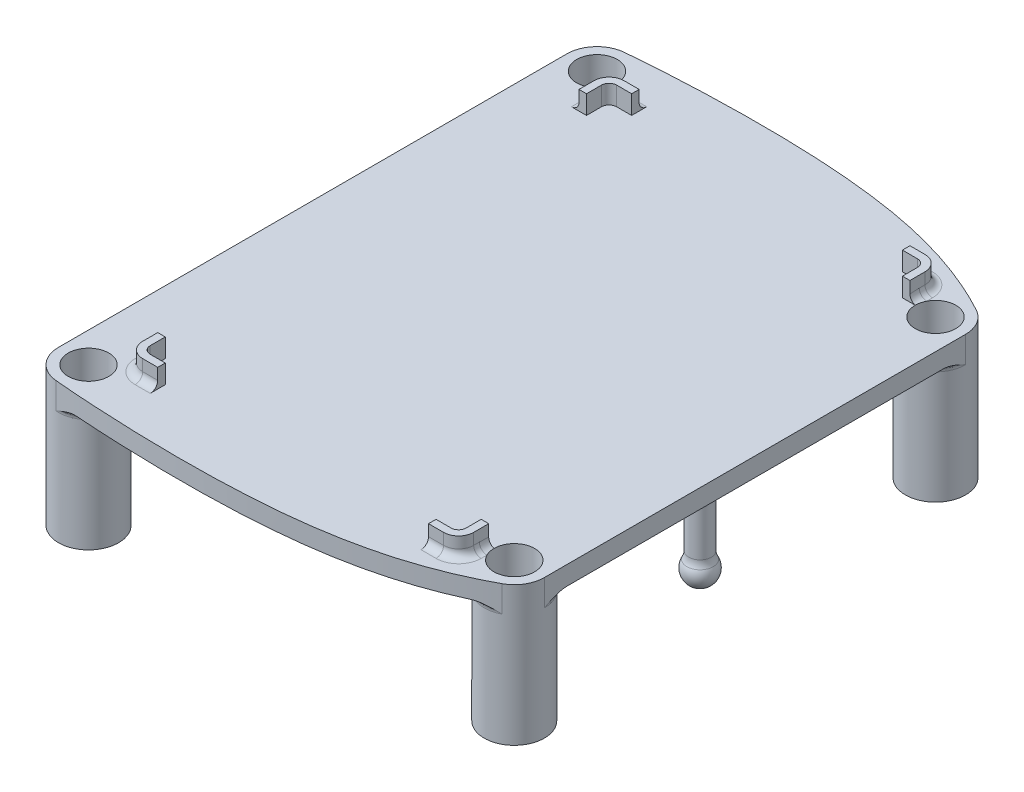
SolidWorks part; units mm, degrees
ref_plane "前视基准面" through (0, 0, 0) normal (0, 0, 1) x (1, 0, 0)
ref_plane "上视基准面" through (0, 0, 0) normal (0, 1, 0) x (1, 0, 0)
ref_plane "右视基准面" through (0, 0, 0) normal (1, 0, 0) x (0, 0, -1)
other "Configuration Table"
sketch "草图1" plane through (0, 0, 0) normal (0, 1, 0) x (1, 0, 0)
  line L0 (0, 35.4779) -> (0, -35.3561) construction
  line L1 (-47.5, 31) -> (-41.5, 31)
  line L2 (-47.5, 25) -> (-47.5, -25)
  line L3 (-47.5, -31) -> (-41.5, -31)
  line L4 (47.5, 25) -> (47.5, -25)
  line L5 (-47.5, 31) -> (47.5, -31) construction
  line L6 (-47.5, -31) -> (47.5, 31) construction
  line L9 (-41.5, 31) -> (-41.5, 41)
  line L11 (-29.5, 31) -> (-29.5, 41)
  line L12 (29.5, 31) -> (29.5, 41)
  line L14 (41.5, 31) -> (41.5, 41)
  line L15 (-78.7463, 0) -> (58.6748, 0) construction
  line L16 (41.5, -31) -> (41.5, -41)
  line L18 (29.5, -31) -> (29.5, -41)
  line L21 (-29.5, -31) -> (-29.5, -41)
  line L23 (-41.5, -31) -> (-41.5, -41)
  line L24 (-29.5, 31) -> (-3, 31)
  line L25 (41.5, 31) -> (47.5, 31)
  line L26 (41.5, -31) -> (47.5, -31)
  line L27 (-29.5, -31) -> (-3, -31)
  line L28 (47.5, 31) -> (50.8, 31)
  line L29 (-47.5, 31) -> (-50.8, 31)
  line L31 (-47.5, 25) -> (-50.8, 25)
  line L33 (47.5, 25) -> (50.8, 25)
  line L36 (47.5, -25) -> (50.8, -25)
  line L37 (47.5, -31) -> (50.8, -31)
  line L38 (-47.5, -31) -> (-50.8, -31)
  line L39 (-47.5, -25) -> (-50.8, -25)
  line L41 (-3, -33.8) -> (-3, -31)
  line L43 (-3, 33.8) -> (-3, 31)
  line L45 (3, 33.8) -> (3, 31)
  line L47 (3, -33.8) -> (3, -31)
  line L48 (3, 31) -> (29.5, 31)
  line L49 (3, -31) -> (29.5, -31)
  arc A0 (-41.5, 41) -> (-29.5, 41) centre (-35.5, 41) cw
  arc A1 (-41.5, -41) -> (-29.5, -41) centre (-35.5, -41) ccw
  arc A2 (41.5, -41) -> (29.5, -41) centre (35.5, -41) cw
  arc A3 (41.5, 41) -> (29.5, 41) centre (35.5, 41) ccw
  arc A4 (-50.8, 31) -> (-50.8, 25) centre (-50.8, 28) ccw
  circle A5 centre (-50.8, 28) radius 1.5
  circle A6 centre (50.8, 28) radius 1.5
  arc A7 (50.8, 31) -> (50.8, 25) centre (50.8, 28) cw
  circle A8 centre (50.8, -28) radius 1.5
  arc A9 (50.8, -31) -> (50.8, -25) centre (50.8, -28) ccw
  circle A10 centre (-50.8, -28) radius 1.5
  arc A11 (-50.8, -31) -> (-50.8, -25) centre (-50.8, -28) cw
  arc A12 (-3, 33.8) -> (3, 33.8) centre (0, 33.8) cw
  circle A13 centre (0, 33.8) radius 1.5
  circle A14 centre (0, -33.8) radius 1.5
  arc A15 (-3, -33.8) -> (3, -33.8) centre (0, -33.8) ccw
  point P0 (0, 0)
  dimension "D8" = 2.8
  dimension "D1" = 95
  dimension "D2" = 62
  dimension "D3" = 83
  dimension "D4" = 12
  dimension "D5" = 10
  dimension "D6" = 3.3
  dimension "D7" = 6
  dimension "D9" = 6
extrude "凸台-拉伸1" add sketch "草图1" against normal blind 15
sketch "草图2" plane through (0, -15, 0) normal (0, -1, 0) x (1, 0, 0)
  line L0 (-63.1336, 0) -> (63.5579, 0) construction
  line L1 (-57.0239, 31) -> (-3, 31)
  line L2 (-57.0239, 31) -> (-57.0239, 48.5806)
  line L3 (-57.0239, 48.5806) -> (57.0239, 48.5806)
  line L4 (57.0239, 31) -> (57.0239, 48.5806)
  line L5 (0, 56.9992) -> (0, -44.1169) construction
  line L6 (3, 33.8) -> (3, 31) construction
  line L7 (-3, 31) -> (-3, 33.8) construction
  line L8 (3, 33.8) -> (3, 31)
  line L9 (-3, 31) -> (-3, 33.8)
  line L10 (3, 31) -> (57.0239, 31)
  line L11 (3, -33.8) -> (3, -31)
  line L12 (-3, -31) -> (-3, -33.8)
  line L13 (-57.0239, -31) -> (-3, -31)
  line L14 (-57.0239, -31) -> (-57.0239, -48.5806)
  line L15 (-57.0239, -48.5806) -> (57.0239, -48.5806)
  line L16 (57.0239, -31) -> (57.0239, -48.5806)
  line L17 (3, -31) -> (57.0239, -31)
  arc A0 (3, 33.8) -> (-3, 33.8) centre (0, 33.8) ccw construction
  arc A1 (3, 33.8) -> (-3, 33.8) centre (0, 33.8) ccw
  arc A2 (3, -33.8) -> (-3, -33.8) centre (0, -33.8) cw
extrude "切除-拉伸1" cut sketch "草图2" against normal blind 11
sketch "草图3" plane through (0, -15, 0) normal (0, -1, 0) x (1, 0, 0)
  line L0 (47.5, 25) -> (47.5, -25) construction
  line L1 (-45, -28.5) -> (45, -28.5)
  line L2 (-45, -28.5) -> (-45, 28.5)
  line L3 (-45, 28.5) -> (45, 28.5)
  line L4 (45, -28.5) -> (45, 28.5)
  line L5 (-45, -28.5) -> (45, 28.5) construction
  line L6 (-45, 28.5) -> (45, -28.5) construction
  line L7 (-50.8, 31) -> (-3, 31) construction
  point P0 (0, 0)
  dimension "D1" = 2.5
  dimension "D2" = 2.5
extrude "切除-拉伸2" cut sketch "草图3" against normal blind 12
sketch "草图4" plane through (0, -4, 0) normal (0, -1, 0) x (1, 0, 0)
  line L0 (-29.5, 41) -> (-41.5, 41) construction
  line L1 (-71.7869, 0) -> (71.1524, 0) construction
  line L2 (0, 61.1393) -> (0, -47.8922) construction
  circle A0 centre (-35.5, 41) radius 2.8
  circle A1 centre (35.5, 41) radius 2.8
  circle A2 centre (35.5, -41) radius 2.8
  circle A3 centre (-35.5, -41) radius 2.8
extrude "凸台-拉伸2" add sketch "草图4" along normal blind 3.3 separate body
sketch "草图5" plane through (0, -7.3, 0) normal (0, -1, 0) x (1, 0, 0)
  line L0 (-58.868, 0) -> (56.1189, 0) construction
  line L1 (0, 46.5823) -> (0, -51.4835) construction
  circle A0 centre (-35.5, 41) radius 1.5
  circle A1 centre (35.5, 41) radius 1.5
  circle A2 centre (35.5, -41) radius 1.5
  circle A3 centre (-35.5, -41) radius 1.5
extrude "凸台-拉伸3" add sketch "草图5" along normal blind 1.3 separate body
sketch "草图6" plane through (0, -15, 0) normal (0, -1, 0) x (1, 0, 0)
  line L0 (-50.8, 31) -> (-3, 31) construction
  line L1 (-47.5, 31) -> (47.5, 31)
  line L2 (-47.5, 31) -> (-47.5, -31)
  line L3 (-47.5, -31) -> (47.5, -31)
  line L4 (47.5, 31) -> (47.5, -31)
  line L5 (50.8, -31) -> (3, -31) construction
extrude "切除-拉伸3" cut sketch "草图6" against normal blind 5
sketch "草图7" plane through (0, -3, 0) normal (0, -1, 0) x (1, 0, 0)
  line L0 (-60.2485, 0) -> (64.067, 0) construction
  line L1 (0, 41.3678) -> (0, -47.8169) construction
  line L2 (-30, -19) -> (30, -19)
  line L3 (-30, 21) -> (-2, 21)
  line L4 (-30, 21) -> (-30, 19)
  line L5 (-30, 19) -> (30, 19)
  line L6 (30, 21) -> (30, 19)
  line L7 (-30, 21) -> (30, 19) construction
  line L8 (-30, 19) -> (30, 21) construction
  line L9 (30, -21) -> (30, -19)
  line L10 (-30, -21) -> (-2, -21)
  line L11 (-30, -21) -> (-30, -19)
  line L12 (45, 28.5) -> (-45, 28.5) construction
  line L13 (-2, 28.5) -> (2, 28.5)
  line L14 (-2, 28.5) -> (-2, 21)
  line L16 (2, 28.5) -> (2, 21)
  line L18 (2, -28.5) -> (2, -21)
  line L19 (-2, -28.5) -> (2, -28.5)
  line L20 (-2, -28.5) -> (-2, -21)
  line L21 (2, 21) -> (30, 21)
  line L22 (2, -21) -> (30, -21)
  point P5 (0, 20)
  dimension "D1" = 19
  dimension "D2" = 2
  dimension "D3" = 60
  dimension "D4" = 4
extrude "凸台-拉伸4" add sketch "草图7" along normal blind 2.5 separate body
sketch "草图9" plane through (0, -10, 0) normal (0, -1, 0) x (1, 0, 0)
  line L0 (-45, 28.5) -> (45, 28.5) construction
  line L1 (41.5, 31) -> (32, 31)
  line L2 (41.5, 31) -> (41.5, 28.5)
  line L3 (41.5, 28.5) -> (32, 28.5)
  line L4 (32, 31) -> (32, 28.5)
  dimension "D1" = 9.5
extrude "切除-拉伸4" cut sketch "草图9" against normal blind 5
sketch "草图10" plane through (0, 0, 0) normal (0, 1, 0) x (1, 0, 0)
  line L1 (-34.25, -14) -> (34.25, -14)
  line L2 (-36.25, -12) -> (-36.25, 12)
  line L3 (-34.25, 14) -> (34.25, 14)
  line L4 (36.25, -12) -> (36.25, 12)
  line L5 (-36.25, -14) -> (36.25, 14) construction
  line L6 (-36.25, 14) -> (36.25, -14) construction
  arc A0 (-34.25, -14) -> (-36.25, -12) centre (-34.25, -12) cw
  arc A1 (34.25, -14) -> (36.25, -12) centre (34.25, -12) ccw
  arc A2 (34.25, 14) -> (36.25, 12) centre (34.25, 12) cw
  arc A3 (-36.25, 12) -> (-34.25, 14) centre (-34.25, 12) cw
  point P0 (0, 0)
  dimension "D3" = 2
  dimension "D1" = 72.5
  dimension "D2" = 28
extrude "切除-拉伸5" cut sketch "草图10" against normal through all
fillet "圆角1" radius 3 8 edges at (41.5, -2, 31) (29.5, -2, 31) (-29.5, -2, 31) (-41.5, -2, 31) (-41.5, -2, -31) (-29.5, -2, -31) (29.5, -2, -31) (41.5, -2, -31)
fillet "圆角3" radius 1 12 edges at (0, -3, -28.5) (-45, -3, 0) (0, -3, 28.5) (45, -3, 0) (-35.6642, -3, -13.4142) (0, -3, -14) (35.6642, -3, -13.4142) (36.25, -3, 0) (35.6642, -3, 13.4142) (0, -3, 14) (-35.6642, -3, 13.4142) (-36.25, -3, 0)
combine bodies "组合1" operation type add bodies to combine 111 121 115 109 112 113 116 110 118 119 114
fillet "圆角4" radius 1 40 edges at (-2, -3, 24.25) (-2, -3, -24.25) (-2, -3.2929, 28.2071) (-2, -3.2929, -28.2071) (-2, -4.75, 28.5) (-2, -4.75, -28.5) (-2, -5.5, 24.75) (-30, -3, 20) (16, -5.5, 21) (0, -5.5, 28.5) (-30, -3, -20) (-2, -5.5, -24.75) (0, -5.5, -28.5) (16, -5.5, -21) (-2, -4.25, 21) (-16, -5.5, 21) (-30, -4.25, 21) (-16, -3, 21) (2, -4.25, 21) (2, -5.5, 24.75) (2, -4.75, 28.5) (2, -3.2929, 28.2071) (2, -3, 24.25) (-30, -4.25, -21) (-16, -5.5, -21) (-2, -4.25, -21) (-16, -3, -21) (2, -5.5, -24.75) (2, -4.25, -21) (2, -3, -24.25) (2, -3.2929, -28.2071) (2, -4.75, -28.5) (-47.5, -5, 25) (-47.5, -5, -25) (-3, -5, -31) (3, -5, -31) (47.5, -5, -25) (47.5, -5, 25) (-3, -5, 31) (3, -5, 31)
sketch "草图11" plane through (0, 0, 0) normal (0, 1, 0) x (1, 0, 0)
  line L0 (-69.2433, 0) -> (76.7956, 0) construction
  circle A0 centre (0, 33.8) radius 4
  circle A1 centre (50.8, 28) radius 4
  circle A2 centre (0, -33.8) radius 4
  circle A3 centre (50.8, -28) radius 4
extrude "凸台-拉伸5" add sketch "草图11" along normal blind 16
sketch "草图12" plane through (0, 16, 0) normal (0, 1, 0) x (1, 0, 0)
  line L0 (-65.6793, 0) -> (77.8139, 0) construction
  circle A0 centre (0, 33.8) radius 1.5
  circle A1 centre (50.8, 28) radius 1.5
  circle A2 centre (0, -33.8) radius 1.5
  circle A3 centre (50.8, -28) radius 1.5
extrude "切除-拉伸6" cut sketch "草图12" against normal up to next
sketch "草图13" plane through (0, 16, 0) normal (0, 1, 0) x (1, 0, 0)
  line L0 (-55.9061, 0) -> (58.1408, 0) construction
  circle A0 centre (0, 33.8) radius 2.7
  circle A1 centre (50.8, 28) radius 2.7
  circle A2 centre (0, -33.8) radius 2.7
  circle A3 centre (50.8, -28) radius 2.7
extrude "切除-拉伸7" cut sketch "草图13" against normal blind 12.5
sketch "草图14" plane through (0, 16, 0) normal (0, 1, 0) x (1, 0, 0)
  line L0 (0, 33.8) -> (0, -33.8) construction
  line L1 (50.8, 28) -> (50.8, -28) construction
  line L2 (-60.003, 0) -> (68.6402, 0) construction
  line L3 (0, 33.8) -> (0, -33.8)
  line L4 (0, 33.8) -> (12.6031, 34.95) construction
  line L5 (12.6031, 34.95) -> (27.419, 34.7819) construction
  line L6 (27.419, 34.7819) -> (38.9454, 34.4297) construction
  line L7 (38.9454, 34.4297) -> (50.8, 28) construction
  line L8 (50.8, 28) -> (50.8, -28)
  line L9 (0, -33.8) -> (12.6031, -34.95) construction
  line L10 (12.6031, -34.95) -> (27.419, -34.7819) construction
  line L11 (27.419, -34.7819) -> (38.9454, -34.4297) construction
  line L12 (38.9454, -34.4297) -> (50.8, -28) construction
  line L13 (54.8, 28) -> (54.8, -28)
  line L14 (-4, 33.8) -> (-4, -33.8)
  line L15 (-4, 37.4516) -> (-4, -37.4516) construction
  line L16 (54.8, 30.381) -> (54.8, -30.381) construction
  arc A0 (3.9878, 34.1116) -> (3.9835, 34.1635) centre (0, 33.8) ccw
  arc A1 (52.7071, -31.5161) -> (54.8, -28) centre (50.8, -28) ccw
  arc A2 (3.9835, -34.1635) -> (3.9878, -34.1116) centre (0, -33.8) ccw
  circle A8 centre (50.8, 28) radius 1.5 construction
  circle A9 centre (0, -33.8) radius 4 construction
  circle A11 centre (50.8, 28) radius 4 construction
  circle A12 centre (0, 33.8) radius 4 construction
  arc A13 (-4, -33.8) -> (0, -37.8) centre (0, -33.8) ccw
  arc A15 (54.8, 28) -> (52.7071, 31.5161) centre (50.8, 28) ccw
  arc A16 (-0.3635, 37.7835) -> (-4, 33.8) centre (0, 33.8) ccw
  spline S0 degree 4 poles (0, 33.8) (12.6031, 34.95) (27.419, 34.7819) (38.9454, 34.4297) (50.8, 28) knots 0 0 0 0 0 1 1 1 1 1
  spline S1 degree 4 poles (0, -33.8) (12.6031, -34.95) (27.419, -34.7819) (38.9454, -34.4297) (50.8, -28) knots 0 0 0 0 0 1 1 1 1 1
  spline S2 degree 1 poles (-4, -37.4516) (54.8, -30.381) knots 0 0 1 1 construction
  spline S3 degree 1 poles (-4, 37.4516) (54.8, 30.381) knots 0 0 1 1 construction
  spline S4 degree 3 poles (54.8, -30.381) (54.2486, -30.68) (53.6303, -31.0154) (52.9472, -31.3859) (52.7924, -31.4698) (52.565, -31.5933) (52.1027, -31.841) (51.093, -32.3627) (49.5916, -33.0832) (47.1986, -34.1154) (44.1982, -35.2065) (39.3793, -36.5763) (33.3024, -37.691) (25.8804, -38.3646) (18.3191, -38.5854) (11.9591, -38.5008) (6.9036, -38.2973) (3.2926, -38.0869) (0.8055, -37.8906) (-0.7075, -37.7519) (-1.3947, -37.6892) (-2.5351, -37.5854) (-3.4138, -37.5051) (-4, -37.4516) knots -0.072135 -0.072135 -0.072135 -0.072135 -0.037252 -0.032891 -0.029088 -0.026907 -0.01981 -0.002368 0.032515 0.067399 0.137166 0.206933 0.346467 0.486001 0.625535 0.765069 0.834836 0.904603 0.967642 0.976363 0.991812 1.009254 1.044138 1.044138 1.044138 1.044138 only from (52.7071, -31.5161) to (-0.3635, -37.7835)
  spline S5 degree 3 poles (-4, 37.4516) (-3.4138, 37.5051) (-2.5351, 37.5854) (-1.3947, 37.6892) (-0.7075, 37.7519) (0.8055, 37.8906) (3.2926, 38.0869) (6.9036, 38.2973) (11.9591, 38.5008) (18.3191, 38.5854) (25.8804, 38.3646) (33.3024, 37.691) (39.3793, 36.5763) (44.1982, 35.2065) (47.1986, 34.1154) (49.5916, 33.0832) (51.093, 32.3627) (52.1027, 31.841) (52.565, 31.5933) (52.7924, 31.4698) (52.9472, 31.3859) (53.6303, 31.0154) (54.2486, 30.68) (54.8, 30.381) knots -0.072135 -0.072135 -0.072135 -0.072135 -0.037252 -0.01981 -0.00436 0.00436 0.067399 0.137166 0.206933 0.346467 0.486001 0.625535 0.765069 0.834836 0.904603 0.939487 0.974371 0.991812 0.99891 1.00109 1.004894 1.009254 1.044138 1.044138 1.044138 1.044138 only from (-0.3635, 37.7835) to (52.7071, 31.5161)
  point P11 (50.8, 0)
  point P17 (0, 0)
  circle M17 centre (0, 33.8) radius 2.7
  circle M18 centre (0, 33.8) radius 4
  dimension "D1" = 4
extrude "凸台-拉伸6" add sketch "草图14" along normal blind 2.5 contours S5 S0 L8 S1 L3 L14 A13 S4 A1 L13 A15 M18 | L3 S1 L8 S0 M18 | S0 L3 M17 M18 | L3 S0 M17 | S0 L3 M17 M18 | S0 L3 M17 region at (1.1785, 16, -32.7167) region at (-0.4217, 16, -34.1876) region at (2.2186, 16, -31.7515) region at (-0.1131, 16, -30.45) region at (24.8986, 16, 0.1265) region at (-0.9694, 16, 2)
sketch "草图15" plane through (0, 18.5, 0) normal (0, 1, 0) x (1, 0, 0)
  line L2 (-4, 33.8) -> (-4, -33.8)
  line L3 (54.8, -28) -> (54.8, 28)
  line L4 (-4, 33.8) -> (-4, -33.8)
  line L5 (54.8, -28) -> (54.8, 28)
  circle A0 centre (0, 33.8) radius 2.7
  circle A1 centre (50.8, 28) radius 2.7
  circle A2 centre (50.8, -28) radius 2.7
  circle A3 centre (0, -33.8) radius 2.7
  arc A4 (-0.3635, 37.7835) -> (-4, 33.8) centre (0, 33.8) ccw
  arc A5 (-4, -33.8) -> (-0.3635, -37.7835) centre (0, -33.8) ccw
  arc A6 (52.7071, -31.5161) -> (54.8, -28) centre (50.8, -28) ccw
  arc A7 (54.8, 28) -> (52.7071, 31.5161) centre (50.8, 28) ccw
  arc A8 (-0.3635, 37.7835) -> (-4, 33.8) centre (0, 33.8) ccw
  arc A9 (-4, -33.8) -> (-0.3635, -37.7835) centre (0, -33.8) ccw
  arc A10 (52.7071, -31.5161) -> (54.8, -28) centre (50.8, -28) ccw
  arc A11 (54.8, 28) -> (52.7071, 31.5161) centre (50.8, 28) ccw
  spline S2 degree 3 poles (-2546.4981, 1528.7201) (61.493, 26.0185) (56.6767, 29.3897) (52.1027, 31.841) (51.093, 32.3627) (49.5916, 33.0832) (47.1986, 34.1154) (44.1982, 35.2065) (39.3793, 36.5763) (33.3024, 37.691) (25.8804, 38.3646) (18.3191, 38.5854) (11.9591, 38.5008) (6.9036, 38.2973) (3.2926, 38.0869) (-15.5497, 36.6001) (-30.0191, 32.3563) (2942.6396, 619.4497) knots -0.238757 -0.238757 -0.238757 -0.238757 0.00109 0.008188 0.025629 0.060513 0.095397 0.165164 0.234931 0.374465 0.513999 0.653533 0.793067 0.862834 0.932601 0.99564 1.935016 1.935016 1.935016 1.935016 only from (52.7071, 31.5161) to (-0.3635, 37.7835)
  spline S3 degree 3 poles (2942.5968, -619.4413) (-30.0189, -32.3564) (-15.5496, -36.6001) (3.2926, -38.0869) (6.9036, -38.2973) (11.9591, -38.5008) (18.3191, -38.5854) (25.8804, -38.3646) (33.3024, -37.691) (39.3793, -36.5763) (44.1982, -35.2065) (47.1986, -34.1154) (49.5916, -33.0832) (51.093, -32.3627) (52.1027, -31.841) (56.6765, -29.3898) (61.4926, -26.0188) (-2546.1335, -1528.51) knots -0.963009 -0.963009 -0.963009 -0.963009 -0.023637 0.039401 0.109168 0.178935 0.318469 0.458004 0.597538 0.737072 0.806839 0.876606 0.911489 0.946373 0.963815 0.970912 1.210749 1.210749 1.210749 1.210749 only from (-0.3635, -37.7835) to (52.7071, -31.5161)
  spline S4 degree 3 poles (52.7071, 31.5161) (52.6884, 31.5263) (52.5461, 31.6034) (52.1027, 31.841) (51.093, 32.3627) (49.5916, 33.0832) (47.1986, 34.1154) (44.1982, 35.2065) (39.3793, 36.5763) (33.3024, 37.691) (25.8804, 38.3646) (18.3191, 38.5854) (11.9591, 38.5008) (6.9036, 38.2973) (3.2926, 38.0869) (0.8821, 37.8967) (-0.2881, 37.7903) (-0.3635, 37.7835) knots 0 0 0 0 0.00109 0.008188 0.025629 0.060513 0.095397 0.165164 0.234931 0.374465 0.513999 0.653533 0.793067 0.862834 0.932601 0.99564 1 1 1 1
  spline S5 degree 3 poles (-0.3635, -37.7835) (-0.2881, -37.7903) (0.8821, -37.8967) (3.2926, -38.0869) (6.9036, -38.2973) (11.9591, -38.5008) (18.3191, -38.5854) (25.8804, -38.3646) (33.3024, -37.691) (39.3793, -36.5763) (44.1982, -35.2065) (47.1986, -34.1154) (49.5916, -33.0832) (51.093, -32.3627) (52.1027, -31.841) (52.5461, -31.6034) (52.6884, -31.5263) (52.7071, -31.5161) knots -0.027998 -0.027998 -0.027998 -0.027998 -0.023637 0.039401 0.109168 0.178935 0.318469 0.458004 0.597538 0.737072 0.806839 0.876606 0.911489 0.946373 0.963815 0.970912 0.972002 0.972002 0.972002 0.972002
  dimension "D1" = 0
extrude "切除-拉伸9" cut sketch "草图15" against normal up to next contours A0 | A1 | A3 | A2 region at (0, 18.5, -33.8) region at (50.8, 18.5, -28) region at (50.8, 18.5, 28) region at (0, 18.5, 33.8)
sketch "草图18" plane through (0, 18.5, 0) normal (0, 1, 0) x (1, 0, 0)
  line L0 (-4, 0) -> (54.8, 0) construction
  line L1 (-4, 33.8) -> (-4, -33.8) construction
  line L2 (54.8, 28) -> (54.8, -28) construction
  line L3 (3.4, 30) -> (3.4, -30)
  line L4 (5.4, 31) -> (45.4, 31)
  line L5 (4.4, 30) -> (4.4, -30)
  line L6 (5.4, -31) -> (45.4, -31)
  line L7 (46.4, 30) -> (46.4, -30)
  line L8 (4.4, 31) -> (46.4, -31) construction
  line L9 (4.4, -31) -> (46.4, 31) construction
  line L10 (5.4, -32) -> (45.4, -32)
  line L11 (47.4, 30) -> (47.4, -30)
  line L12 (5.4, 32) -> (45.4, 32)
  line L13 (7.4, 32) -> (7.4, 31)
  line L14 (3.4, 28) -> (4.4, 28)
  line L15 (7.4, -32) -> (7.4, -31)
  line L16 (3.4, -28) -> (4.4, -28)
  line L17 (25.4, 35.8449) -> (25.4, -33.7801) construction
  line L18 (47.4, -28) -> (46.4, -28)
  line L19 (43.4, -32) -> (43.4, -31)
  line L20 (47.4, 28) -> (46.4, 28)
  line L21 (43.4, 32) -> (43.4, 31)
  arc A0 (45.4, -31) -> (46.4, -30) centre (45.4, -30) ccw
  arc A1 (4.4, -30) -> (5.4, -31) centre (5.4, -30) ccw
  arc A2 (45.4, 31) -> (46.4, 30) centre (45.4, 30) cw
  arc A3 (5.4, 31) -> (4.4, 30) centre (5.4, 30) ccw
  arc A4 (3.4, -30) -> (5.4, -32) centre (5.4, -30) ccw
  arc A5 (45.4, -32) -> (47.4, -30) centre (45.4, -30) ccw
  arc A6 (45.4, 32) -> (47.4, 30) centre (45.4, 30) cw
  arc A7 (5.4, 32) -> (3.4, 30) centre (5.4, 30) ccw
  point P6 (25.4, 0)
  dimension "D3" = 1
  dimension "D1" = 62
  dimension "D2" = 42
  dimension "D5" = 2
  dimension "D6" = 2
  dimension "D4" = 1
extrude "凸台-拉伸8" add sketch "草图18" along normal blind 2.5 contours L3 A4 L10 L15 L6 A1 L5 L16 | L10 A5 L11 L18 L7 A0 L6 L19 | A6 L12 L21 L4 A2 L7 L20 L11 | L12 A7 L3 L14 L5 A3 L4 L13 region at (4.0258, 18.5, -31.3742) region at (3.9, 18.5, 28.0566) region at (44.4, 18.5, -31.9434) region at (43.4566, 18.5, 31.5)
fillet "圆角5" radius 1 12 edges at (44.4, 18.5, -32) (47.4, 18.5, -29) (44.4, 18.5, 32) (47.4, 18.5, 29) (6.4, 18.5, 32) (3.9858, 18.5, 31.4142) (6.4, 18.5, -32) (3.4, 18.5, -29) (46.8142, 18.5, -31.4142) (46.8142, 18.5, 31.4142) (3.4, 18.5, 29) (3.9858, 18.5, -31.4142)
sketch "草图19" plane through (47.5, 0, 0) normal (1, 0, 0) x (0, 0, -1)
  line L0 (0, 9.0073) -> (0, -13.2174) construction
  line L1 (0, 9.0073) -> (0, -13.2174) construction
  line L2 (0, 9.0073) -> (0, -13.2174) construction
  line L3 (-24, 0) -> (24, 0) construction
  line L4 (0, 3.85) -> (0, 0)
  line L5 (-1.5, 16) -> (-1.5, 3.9365)
  line L6 (28, 16) -> (-28, 16) construction
  line L7 (0, 3.85) -> (0, 16)
  line L8 (0, 16) -> (-1.5, 16)
  arc A0 (-1.75, 2.9682) -> (0, 0) centre (0, 2) ccw
  arc A1 (-1.5, 3.9365) -> (-1.75, 2.9682) centre (-3.5, 3.9365) cw
  dimension "D3" = 2
  dimension "D5" = 2
  dimension "D1" = 0
  dimension "D2" = 2
  dimension "D4" = 1.5
revolve "旋转1" add sketch "草图19" angle 360 about L1
sketch "草图20" plane through (0, 0, 0) normal (0, 1, 0) x (1, 0, 0)
  line L1 (-62.2942, 50.7869) -> (60.6636, 50.7869)
  line L2 (-62.2942, 50.7869) -> (-62.2942, -49.2595)
  line L3 (-62.2942, -49.2595) -> (60.6636, -49.2595)
  line L4 (60.6636, 50.7869) -> (60.6636, -49.2595)
extrude "切除-拉伸11" cut sketch "草图20" against normal through all
fillet "圆角6" radius 1 4 edges at (47.3628, 16, -25.9541) (47.3628, 16, 25.9541) (2.9541, 16, 31.1031) (2.9541, 16, -31.1031)
